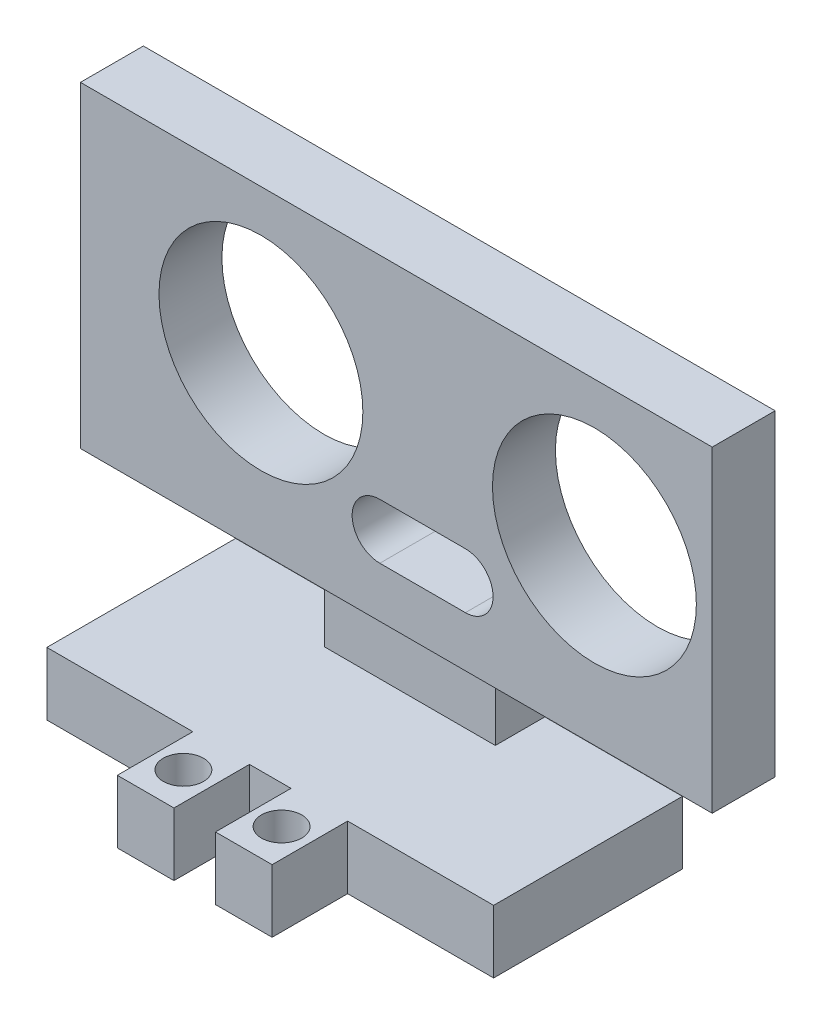
SolidWorks part; units mm, degrees
ref_plane "Front Plane" through (0, 0, 0) normal (0, 0, 1) x (1, 0, 0)
ref_plane "Top Plane" through (0, 0, 0) normal (0, 1, 0) x (1, 0, 0)
ref_plane "Right Plane" through (0, 0, 0) normal (1, 0, 0) x (0, 0, -1)
sketch "Sketch1" plane through (0, 0, 0) normal (0, 1, 0) x (1, 0, 0)
  line L0 (12.7692, 9.9599) -> (48.2692, 9.9599)
  line L5 (12.7692, 21.2754) -> (24.3692, 21.2754)
  line L10 (12.7692, 21.2754) -> (12.7692, 6.2754)
  line L11 (12.7692, 6.2754) -> (24.3692, 6.2754)
  line L12 (48.2692, 21.2754) -> (48.2692, 6.2754)
  line L13 (12.7692, 14.0701) -> (48.2692, 14.1179)
  line L21 (28.8692, 21.2754) -> (32.1692, 21.2754)
  line L22 (36.6692, 21.2754) -> (48.2692, 21.2754)
  line L23 (24.3692, 21.2754) -> (28.8692, 21.2754)
  line L24 (32.1692, 21.2754) -> (36.6692, 21.2754)
  line L25 (24.3692, 0.2754) -> (24.3692, 6.2754)
  line L26 (24.3692, 0.2754) -> (28.8692, 0.2754)
  line L27 (28.8692, 0.2754) -> (28.8692, 6.2754)
  line L28 (32.1692, 0.2754) -> (32.1692, 6.2754)
  line L29 (32.1692, 0.2754) -> (36.6692, 0.2754)
  line L30 (36.6692, 0.2754) -> (36.6692, 6.2754)
  line L31 (28.8692, 6.2754) -> (32.1692, 6.2754)
  line L32 (36.6692, 6.2754) -> (48.2692, 6.2754)
  dimension "D3" = 3.3
  dimension "D4" = 11.6
  dimension "D5" = 4.5
  dimension "D6" = 4.5
  dimension "D1" = 35.5
  dimension "D2" = 15
  dimension "D7" = 6
  dimension "D8" = 6
extrude "Boss-Extrude7" add sketch "Sketch1" along normal blind 5 contours L13 L12 L5 L10 | L13 L10 L0 L12 | L0 L10 L11 L12 region at (30.5534, 0, -12.0269) region at (30.5192, 0, -6.7027) region at (30.4995, 0, -17.6847)
sketch "Sketch5" plane through (0, 5, 0) normal (0, 1, 0) x (1, 0, 0)
  line L0 (12.7692, 21.2754) -> (48.2692, 21.2754) construction
  line L1 (23.7692, 21.2754) -> (37.3363, 21.2754)
  line L2 (23.7692, 21.2754) -> (23.7692, 17.3426)
  line L3 (23.7692, 17.3426) -> (37.3363, 17.3426)
  line L4 (37.3363, 21.2754) -> (37.3363, 17.3426)
  line L5 (12.7692, 21.2754) -> (12.7692, 6.2754) construction
  dimension "D1" = 11
  dimension "D2" = 13.5671
extrude "Boss-Extrude8" add sketch "Sketch5" along normal blind 5
sketch "Sketch6" plane through (1.1246, 10, 0) normal (0, 1, 0) x (1, 0, 0)
  line L0 (11.6446, 21.2754) -> (11.6446, 6.2754) construction
  line L2 (4.2946, 21.2948) -> (54.4946, 21.2948)
  line L3 (4.2946, 21.2948) -> (4.2946, 16.2948)
  line L4 (4.2946, 16.2948) -> (54.4946, 16.2948)
  line L5 (54.4946, 21.2948) -> (54.4946, 16.2948)
  dimension "D1" = 50.2
  dimension "D2" = 5
  dimension "D3" = 7.35
extrude "Boss-Extrude9" add sketch "Sketch6" along normal blind 25.2 contours L3 L2 L5 L4
sketch "Sketch7" plane through (0, 0, -16.2948) normal (0, 0, 1) x (1, 0, 0)
  line L0 (19.7589, 23.75) -> (46.2589, 23.75)
  line L1 (5.4192, 10) -> (55.6192, 10) construction
  line L2 (29.2061, 16.2) -> (36.0061, 16.2) construction
  line L3 (29.2061, 18.4) -> (36.0061, 18.4)
  line L4 (29.2061, 14) -> (36.0061, 14)
  circle A0 centre (19.7589, 23.75) radius 8.1
  circle A1 centre (46.2589, 23.75) radius 8.1
  arc A2 (29.2061, 18.4) -> (29.2061, 14) centre (29.2061, 16.2) ccw
  arc A3 (36.0061, 14) -> (36.0061, 18.4) centre (36.0061, 16.2) ccw
  point P8 (32.6061, 16.2)
  dimension "D1" = 16.2
  dimension "D4" = 2.2
  dimension "D2" = 26.5
  dimension "D3" = 6.8
  dimension "D5" = 5.35
  dimension "D6" = 4
extrude "Cut-Extrude1" cut sketch "Sketch7" against normal blind 10 contours A0 | A1 region at (46.2589, 31.6209, -16.2948) region at (11.888, 23.75, -16.2948)
extrude "Cut-Extrude2" cut sketch "Sketch7<3>" against normal blind 10 contours L4 A3 L3 A2 region at (32.6061, 16.2, -16.2948)
sketch "Sketch7<3>" plane through (0, 0, -16.2948) normal (0, 0, 1) x (1, 0, 0) same geometry as "Sketch7"
sketch "Sketch9" plane through (0, 5, 0) normal (0, 1, 0) x (1, 0, 0)
  line L0 (32.1692, 3.2754) -> (36.6692, 3.2754) construction
  line L3 (24.3692, 3.2754) -> (28.8692, 3.2754) construction
  line L4 (24.3692, 0.2754) -> (24.3692, 6.2754) construction
  line L5 (28.8692, 0.2754) -> (28.8692, 6.2754) construction
  line L6 (32.1692, 0.2754) -> (32.1692, 6.2754) construction
  line L7 (36.6692, 0.2754) -> (36.6692, 6.2754) construction
  circle A0 centre (26.6192, 3.2754) radius 1.6
  circle A1 centre (34.4192, 3.2754) radius 1.6
  dimension "D1" = 3.2
  dimension "D2" = 3.2
extrude "Cut-Extrude4" cut sketch "Sketch9" against normal blind 10 contours A0 | A1
